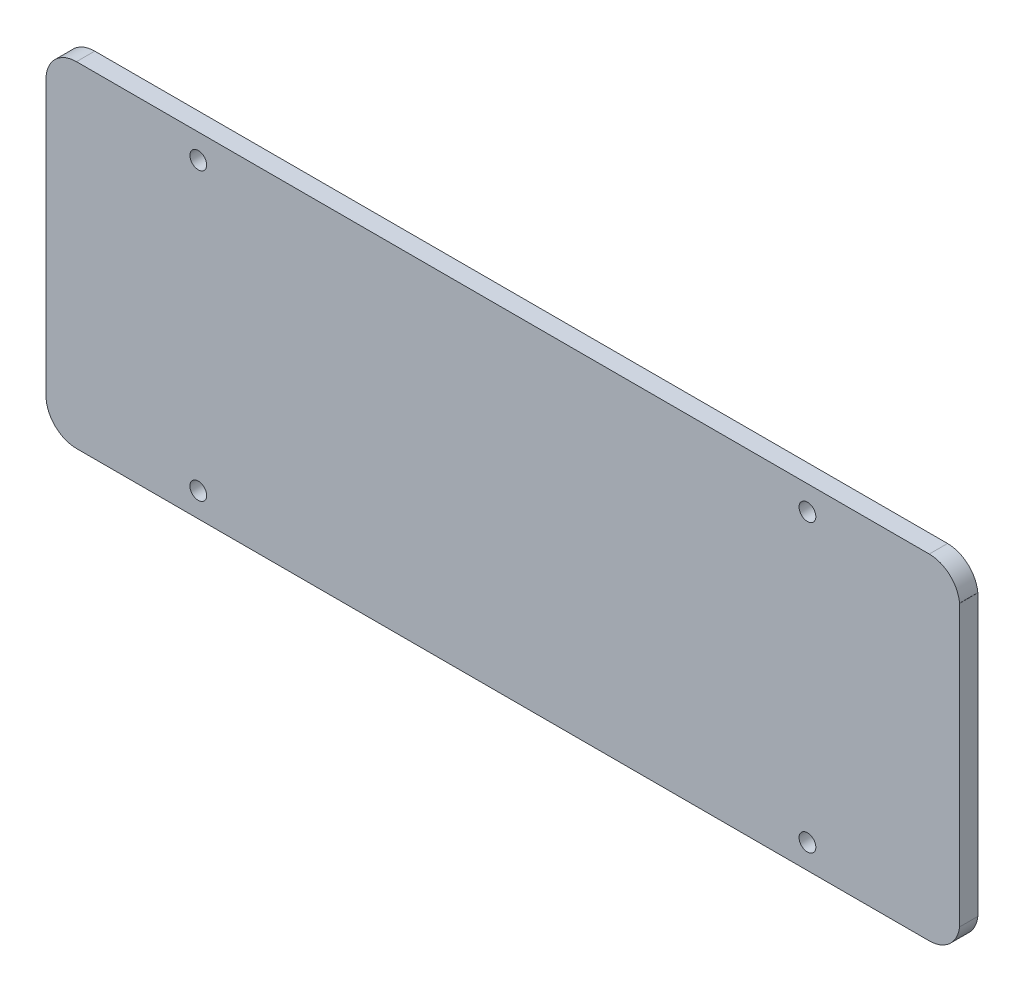
SolidWorks part; units mm, degrees
material "Aircraft Ply"
ref_plane "Front Plane" through (0, 0, 0) normal (0, 0, 1) x (1, 0, 0)
ref_plane "Top Plane" through (0, 0, 0) normal (0, 1, 0) x (1, 0, 0)
ref_plane "Right Plane" through (0, 0, 0) normal (1, 0, 0) x (0, 0, -1)
sketch "Sketch1" plane through (0, 0, 0) normal (0, 0, 1) x (1, 0, 0)
  line L0 (-75, 8) -> (75, 8) construction
  line L1 (-75, 0) -> (75, 0) construction
  line L8 (-75, 23) -> (-75, -23)
  line L9 (-44.3417, -23) -> (-25.6583, -23)
  line L10 (-14.3417, -23) -> (14.3417, -23)
  line L11 (25.6583, -23) -> (44.3417, -23)
  line L12 (75, -23) -> (75, 23)
  line L13 (44.3417, 23) -> (25.6583, 23)
  line L14 (14.3417, 23) -> (-14.3417, 23)
  line L15 (-25.6583, 23) -> (-44.3417, 23)
  line L16 (-75, 23) -> (-75, -23)
  line L17 (-44.3417, -23) -> (-25.6583, -23)
  line L18 (-14.3417, -23) -> (14.3417, -23)
  line L19 (25.6583, -23) -> (44.3417, -23)
  line L20 (75, -23) -> (75, 23)
  line L21 (44.3417, 23) -> (25.6583, 23)
  line L22 (14.3417, 23) -> (-14.3417, 23)
  line L23 (-25.6583, 23) -> (-44.3417, 23)
  line L30 (-75, -23) -> (-55.6583, -23)
  line L31 (-75, -23) -> (-55.6583, -23)
  line L32 (55.6583, -23) -> (75, -23)
  line L33 (55.6583, -23) -> (75, -23)
  line L34 (75, 23) -> (55.6583, 23)
  line L35 (75, 23) -> (55.6583, 23)
  line L36 (-55.6583, 23) -> (-75, 23)
  line L37 (-55.6583, 23) -> (-75, 23)
  line L38 (-51, 10.0616) -> (-51, 5.9384)
  line L39 (-59, 10.0616) -> (-59, 5.9384)
  line L40 (-27, 10.0616) -> (-27, 5.9384)
  line L41 (-19, 10.0616) -> (-19, 5.9384)
  line L42 (5, 10.0616) -> (5, 5.9384)
  line L43 (13, 10.0616) -> (13, 5.9384)
  line L44 (37, 10.0616) -> (37, 5.9384)
  line L45 (45, 10.0616) -> (45, 5.9384)
  line L46 (-11, -5.9384) -> (-11, -10.0616)
  line L47 (-3, -5.9384) -> (-3, -10.0616)
  line L48 (21, -5.9384) -> (21, -10.0616)
  line L49 (29, -5.9384) -> (29, -10.0616)
  line L50 (53, -5.9384) -> (53, -10.0616)
  line L51 (61, -5.9384) -> (61, -10.0616)
  line L52 (-43, -5.9384) -> (-43, -10.0616)
  line L53 (-35, -5.9384) -> (-35, -10.0616)
  circle A0 centre (-50, 23.5) radius 1.375 construction
  circle A1 centre (-20, 23.5) radius 1.375 construction
  circle A2 centre (20, 23.5) radius 1.375 construction
  circle A3 centre (50, 23.5) radius 1.375 construction
  circle A4 centre (50, -23.5) radius 1.375 construction
  circle A5 centre (20, -23.5) radius 1.375 construction
  circle A6 centre (-20, -23.5) radius 1.375 construction
  circle A7 centre (-50, -23.5) radius 1.375 construction
  circle A8 centre (-50, -23.5) radius 1.375
  circle A9 centre (-20, -23.5) radius 1.375
  circle A10 centre (20, -23.5) radius 1.375
  circle A11 centre (50, -23.5) radius 1.375
  circle A12 centre (50, 23.5) radius 1.375
  circle A13 centre (20, 23.5) radius 1.375
  circle A14 centre (-20, 23.5) radius 1.375
  circle A15 centre (-50, 23.5) radius 1.375
  circle A16 centre (-55, 8) radius 4.5
  circle A17 centre (-23, 8) radius 4.5
  circle A18 centre (9, 8) radius 4.5
  circle A19 centre (41, 8) radius 4.5
  circle A20 centre (-39, -8) radius 4.5
  circle A21 centre (-7, -8) radius 4.5
  circle A22 centre (25, -8) radius 4.5
  circle A23 centre (57, -8) radius 4.5
  arc A29 (-54, -23.5) -> (-55.6583, -23) centre (-55.6583, -26) ccw
  arc A30 (-54, -23.5) -> (-46, -23.5) centre (-50, -23.5) ccw
  arc A31 (-44.3417, -23) -> (-46, -23.5) centre (-44.3417, -26) ccw
  arc A32 (-24, -23.5) -> (-25.6583, -23) centre (-25.6583, -26) ccw
  arc A33 (-24, -23.5) -> (-16, -23.5) centre (-20, -23.5) ccw
  arc A34 (-14.3417, -23) -> (-16, -23.5) centre (-14.3417, -26) ccw
  arc A35 (16, -23.5) -> (14.3417, -23) centre (14.3417, -26) ccw
  arc A36 (16, -23.5) -> (24, -23.5) centre (20, -23.5) ccw
  arc A37 (25.6583, -23) -> (24, -23.5) centre (25.6583, -26) ccw
  arc A38 (46, -23.5) -> (44.3417, -23) centre (44.3417, -26) ccw
  arc A39 (46, -23.5) -> (54, -23.5) centre (50, -23.5) ccw
  arc A40 (55.6583, -23) -> (54, -23.5) centre (55.6583, -26) ccw
  arc A43 (54, 23.5) -> (55.6583, 23) centre (55.6583, 26) ccw
  arc A44 (54, 23.5) -> (46, 23.5) centre (50, 23.5) ccw
  arc A45 (44.3417, 23) -> (46, 23.5) centre (44.3417, 26) ccw
  arc A46 (24, 23.5) -> (25.6583, 23) centre (25.6583, 26) ccw
  arc A47 (24, 23.5) -> (16, 23.5) centre (20, 23.5) ccw
  arc A48 (14.3417, 23) -> (16, 23.5) centre (14.3417, 26) ccw
  arc A49 (-16, 23.5) -> (-14.3417, 23) centre (-14.3417, 26) ccw
  arc A50 (-16, 23.5) -> (-24, 23.5) centre (-20, 23.5) ccw
  arc A51 (-25.6583, 23) -> (-24, 23.5) centre (-25.6583, 26) ccw
  arc A52 (-46, 23.5) -> (-44.3417, 23) centre (-44.3417, 26) ccw
  arc A53 (-46, 23.5) -> (-54, 23.5) centre (-50, 23.5) ccw
  arc A54 (-55.6583, 23) -> (-54, 23.5) centre (-55.6583, 26) ccw
  arc A57 (-54, -23.5) -> (-55.6583, -23) centre (-55.6583, -26) ccw
  arc A58 (-54, -23.5) -> (-46, -23.5) centre (-50, -23.5) ccw
  arc A59 (-44.3417, -23) -> (-46, -23.5) centre (-44.3417, -26) ccw
  arc A60 (-24, -23.5) -> (-25.6583, -23) centre (-25.6583, -26) ccw
  arc A61 (-24, -23.5) -> (-16, -23.5) centre (-20, -23.5) ccw
  arc A62 (-14.3417, -23) -> (-16, -23.5) centre (-14.3417, -26) ccw
  arc A63 (16, -23.5) -> (14.3417, -23) centre (14.3417, -26) ccw
  arc A64 (16, -23.5) -> (24, -23.5) centre (20, -23.5) ccw
  arc A65 (25.6583, -23) -> (24, -23.5) centre (25.6583, -26) ccw
  arc A66 (46, -23.5) -> (44.3417, -23) centre (44.3417, -26) ccw
  arc A67 (46, -23.5) -> (54, -23.5) centre (50, -23.5) ccw
  arc A68 (55.6583, -23) -> (54, -23.5) centre (55.6583, -26) ccw
  arc A71 (54, 23.5) -> (55.6583, 23) centre (55.6583, 26) ccw
  arc A72 (54, 23.5) -> (46, 23.5) centre (50, 23.5) ccw
  arc A73 (44.3417, 23) -> (46, 23.5) centre (44.3417, 26) ccw
  arc A74 (24, 23.5) -> (25.6583, 23) centre (25.6583, 26) ccw
  arc A75 (24, 23.5) -> (16, 23.5) centre (20, 23.5) ccw
  arc A76 (14.3417, 23) -> (16, 23.5) centre (14.3417, 26) ccw
  arc A77 (-16, 23.5) -> (-14.3417, 23) centre (-14.3417, 26) ccw
  arc A78 (-16, 23.5) -> (-24, 23.5) centre (-20, 23.5) ccw
  arc A79 (-25.6583, 23) -> (-24, 23.5) centre (-25.6583, 26) ccw
  arc A80 (-46, 23.5) -> (-44.3417, 23) centre (-44.3417, 26) ccw
  arc A81 (-46, 23.5) -> (-54, 23.5) centre (-50, 23.5) ccw
  arc A82 (-55.6583, 23) -> (-54, 23.5) centre (-55.6583, 26) ccw
  dimension "D2" = 9
  dimension "D3" = 8
  dimension "D6" = 20
  dimension "D7" = 8
  dimension "D1" = 0
  dimension "D4" = 4
  dimension "D5" = 2
extrude "Boss-Extrude1" add sketch "Sketch1" along normal blind 3 contours A82 L37 L16 L31 A57 A58 A59 L17 A60 A61 A62 L18 A63 A64 A65 L19 A66 A67 A68 L33 L20 L35 A71 A72 A73 L21 A74 A75 A76 L22 A77 A78 A79 L23 A80 A81 A23 A22 A21 | L39 A16 | L38 A16 | L40 A17 | L41 A17 | L42 A18 | L43 A18 | L44 A19 | L45 A19 | L50 A23 | L51 A23 | L48 A22 | L49 A22 | L46 A21 | L47 A21 | L52 A20 | L53 A20 region at (-0.0773, 0, 0) region at (-50.799, 8, 0) region at (-59.201, 8, 0) region at (-27.201, 8, 0) region at (-18.799, 8, 0) region at (4.799, 8, 0) region at (13.201, 8, 0) region at (36.799, 8, 0) region at (45.201, 8, 0) region at (-11.201, -8, 0) region at (-2.799, -8, 0) region at (20.799, -8, 0) region at (29.201, -8, 0) region at (52.799, -8, 0) region at (61.201, -8, 0) region at (-43.201, -8, 0) region at (-34.799, -8, 0)
sketch "Sketch2" plane through (0, 0, 3) normal (0, 0, 1) x (1, 0, 0)
  line L0 (-55, 8) -> (-39, -8) construction
  line L1 (-48.3527, 14.6473) -> (-32.3527, -1.3527)
  line L2 (-61.6473, 1.3527) -> (-45.6473, -14.6473)
  line L3 (-23, 8) -> (-7, -8) construction
  line L4 (-16.3527, 14.6473) -> (-0.3527, -1.3527)
  line L5 (-29.6473, 1.3527) -> (-13.6473, -14.6473)
  line L6 (25, -8) -> (9, 8) construction
  line L7 (18.3527, -14.6473) -> (2.3527, 1.3527)
  line L8 (31.6473, -1.3527) -> (15.6473, 14.6473)
  line L9 (41, 8) -> (57, -8) construction
  line L10 (47.6473, 14.6473) -> (63.6473, -1.3527)
  line L11 (34.3527, 1.3527) -> (50.3527, -14.6473)
  arc A10 (-48.3527, 14.6473) -> (-61.6473, 1.3527) centre (-55, 8) ccw
  arc A11 (-45.6473, -14.6473) -> (-32.3527, -1.3527) centre (-39, -8) ccw
  arc A12 (-16.3527, 14.6473) -> (-29.6473, 1.3527) centre (-23, 8) ccw
  arc A13 (-13.6473, -14.6473) -> (-0.3527, -1.3527) centre (-7, -8) ccw
  arc A14 (18.3527, -14.6473) -> (31.6473, -1.3527) centre (25, -8) ccw
  arc A15 (15.6473, 14.6473) -> (2.3527, 1.3527) centre (9, 8) ccw
  arc A16 (47.6473, 14.6473) -> (34.3527, 1.3527) centre (41, 8) ccw
  arc A17 (50.3527, -14.6473) -> (63.6473, -1.3527) centre (57, -8) ccw
  text T0 "      1" font "Century Gothic" height in points 18
  point P2 (-47, 0)
  point P7 (-15, 0)
  point P14 (17, 0)
  point P21 (49, 0)
sketch "Sketch3" plane through (0, 0, 0) normal (0, 0, 1) x (1, 0, 0)
  line L0 (75, -23) -> (75, 23) construction
  line L1 (-70, 27.5) -> (70, 27.5)
  line L2 (-75, 22.5) -> (-75, -22.5)
  line L3 (-70, -27.5) -> (70, -27.5)
  line L4 (75, 22.5) -> (75, -22.5)
  line L5 (-75, 23) -> (-75, -23) construction
  arc A0 (-46, 23.5) -> (-54, 23.5) centre (-50, 23.5) ccw construction
  arc A1 (-54, -23.5) -> (-46, -23.5) centre (-50, -23.5) ccw construction
  arc A2 (-75, -22.5) -> (-70, -27.5) centre (-70, -22.5) ccw
  arc A3 (70, -27.5) -> (75, -22.5) centre (70, -22.5) ccw
  arc A4 (70, 27.5) -> (75, 22.5) centre (70, 22.5) cw
  arc A5 (-70, 27.5) -> (-75, 22.5) centre (-70, 22.5) ccw
  circle A6 centre (-50, 23.5) radius 1.375
  circle A7 centre (50, 23.5) radius 1.375
  circle A8 centre (50, -23.5) radius 1.375
  circle A9 centre (-50, -23.5) radius 1.375
  dimension "D1" = 5
extrude "Boss-Extrude2" add sketch "Sketch3" along normal through all
